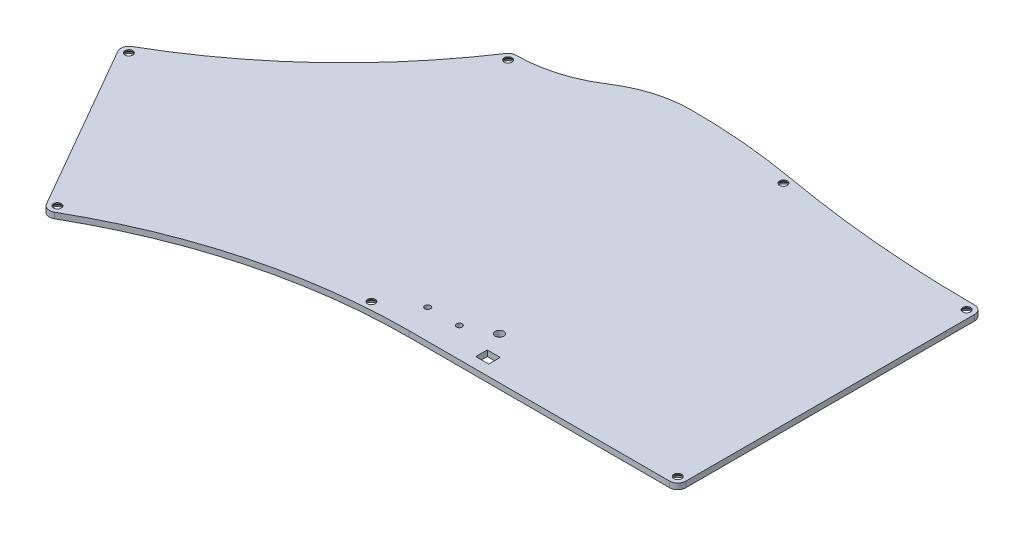
SolidWorks part; units mm, degrees
ref_plane "Front Plane" through (0, 0, 0) normal (0, 0, 1) x (1, 0, 0)
ref_plane "Top Plane" through (0, 0, 0) normal (0, 1, 0) x (1, 0, 0)
ref_plane "Right Plane" through (0, 0, 0) normal (1, 0, 0) x (0, 0, -1)
sketch "Main_line" plane through (0, 0, 0) normal (0, 1, 0) x (1, 0, 0)
  line L17 (146.7823, -115.9715) -> (146.7823, -15.4715)
  line L18 (53.0696, -118.9715) -> (143.7823, -118.9715)
  line L19 (-81.9059, -85.3079) -> (-48.2619, -143.8257)
  line L20 (146.7823, -115.9715) -> (146.7823, -15.4715) construction
  line L21 (53.0696, -118.9715) -> (143.7823, -118.9715) construction
  line L22 (-81.9059, -85.3079) -> (-48.2619, -143.8257) construction
  circle A0 centre (69.7823, -103.9715) radius 1.5 construction
  arc A124 (143.7823, -118.9715) -> (146.7823, -115.9715) centre (143.7823, -115.9715) ccw
  arc A125 (53.0696, -118.9715) -> (-44.1658, -144.9312) centre (53.0696, -314.055) ccw
  arc A126 (-48.2619, -143.8257) -> (-44.1658, -144.9312) centre (-45.6611, -142.3304) ccw
  arc A127 (-80.8004, -81.2119) -> (-81.9059, -85.3079) centre (-79.3051, -83.8126) ccw
  arc A128 (-80.8004, -81.2119) -> (-13.717, -18.312) centre (-180.7133, 92.5689) ccw
  arc A129 (-11.2177, -16.9715) -> (-13.717, -18.312) centre (-11.2177, -19.9715) ccw
  arc A130 (-11.2177, -16.9715) -> (13.3766, -9.6455) centre (-11.2177, 27.9749) ccw
  arc A131 (35.7823, -2.9715) -> (13.3766, -9.6455) centre (35.7823, -43.9179) ccw
  arc A132 (73.4331, -6.2834) -> (35.7823, -2.9715) centre (35.7823, -218.6428) ccw
  arc A133 (73.4331, -6.2834) -> (143.7823, -12.4715) centre (143.7823, 390.502) ccw
  arc A134 (146.7823, -15.4715) -> (143.7823, -12.4715) centre (143.7823, -15.4715) ccw
  arc A135 (143.7823, -118.9715) -> (146.7823, -115.9715) centre (143.7823, -115.9715) ccw construction
  arc A136 (53.0696, -118.9715) -> (-44.1658, -144.9312) centre (53.0696, -314.055) ccw construction
  arc A137 (-48.2619, -143.8257) -> (-44.1658, -144.9312) centre (-45.6611, -142.3304) ccw construction
  arc A138 (-80.8004, -81.2119) -> (-81.9059, -85.3079) centre (-79.3051, -83.8126) ccw construction
  arc A139 (-80.8004, -81.2119) -> (-13.717, -18.312) centre (-180.7133, 92.5689) ccw construction
  arc A140 (-11.2177, -16.9715) -> (-13.717, -18.312) centre (-11.2177, -19.9715) ccw construction
  arc A141 (-11.2177, -16.9715) -> (13.3766, -9.6455) centre (-11.2177, 27.9749) ccw construction
  arc A142 (35.7823, -2.9715) -> (13.3766, -9.6455) centre (35.7823, -43.9179) ccw construction
  arc A143 (73.4331, -6.2834) -> (35.7823, -2.9715) centre (35.7823, -218.6428) ccw construction
  arc A144 (73.4331, -6.2834) -> (143.7823, -12.4715) centre (143.7823, 390.502) ccw construction
  arc A145 (146.7823, -15.4715) -> (143.7823, -12.4715) centre (143.7823, -15.4715) ccw construction
  circle A146 centre (143.7823, -115.9715) radius 1.35 construction
  circle A147 centre (143.7823, -115.9715) radius 1.35 construction
  circle A148 centre (37.7823, -116.5623) radius 1.35 construction
  circle A149 centre (-45.6611, -142.3304) radius 1.35 construction
  circle A150 centre (-79.3051, -83.8126) radius 1.35 construction
  circle A151 centre (-11.2177, -19.9715) radius 1.35 construction
  circle A152 centre (73.7823, -9.2049) radius 1.35 construction
  circle A153 centre (143.7823, -15.4715) radius 1.35 construction
  point P13 (0, 0)
  point P14 (37.7823, -116.5623)
  dimension "D2" = 77
  dimension "D3" = 15
  dimension "D4" = 3
  dimension "D1" = 0
sketch "Sketch1" plane through (0, 0, 0) normal (0, 1, 0) x (1, 0, 0)
  line L17 (-81.7325, -85.2082) -> (-48.0885, -143.726)
  line L18 (53.0696, -118.7715) -> (143.7823, -118.7715)
  line L19 (146.5823, -115.9715) -> (146.5823, -15.4715)
  line L20 (-81.7325, -85.2082) -> (-48.0885, -143.726)
  line L21 (53.0696, -118.7715) -> (143.7823, -118.7715)
  line L22 (146.5823, -115.9715) -> (146.5823, -15.4715)
  circle A93 centre (143.7823, -15.4715) radius 1.35
  circle A94 centre (143.7823, -15.4715) radius 1.35 construction
  circle A95 centre (73.7823, -9.2049) radius 1.35
  circle A96 centre (-11.2177, -19.9715) radius 1.35
  circle A97 centre (-79.3051, -83.8126) radius 1.35
  circle A98 centre (-45.6611, -142.3304) radius 1.35
  circle A99 centre (37.7823, -116.5623) radius 1.35
  circle A100 centre (143.7823, -115.9715) radius 1.35
  circle A101 centre (69.7823, -103.9715) radius 1.5
  circle A102 centre (69.7823, -103.9715) radius 1.5 construction
  arc A103 (-80.7007, -81.3852) -> (-81.7325, -85.2082) centre (-79.3051, -83.8126) ccw
  arc A104 (-48.0885, -143.726) -> (-44.2655, -144.7578) centre (-45.6611, -142.3304) ccw
  arc A105 (53.0696, -118.7715) -> (-44.2655, -144.7578) centre (53.0696, -314.055) ccw
  arc A106 (143.7823, -118.7715) -> (146.5823, -115.9715) centre (143.7823, -115.9715) ccw
  arc A107 (146.5823, -15.4715) -> (143.7823, -12.6715) centre (143.7823, -15.4715) ccw
  arc A108 (73.3982, -6.4803) -> (143.7823, -12.6715) centre (143.7823, 390.502) ccw
  arc A109 (73.3982, -6.4803) -> (35.7823, -3.1715) centre (35.7823, -218.6428) ccw
  arc A110 (35.7823, -3.1715) -> (13.4861, -9.8129) centre (35.7823, -43.9179) ccw
  arc A111 (-11.2177, -17.1715) -> (13.4861, -9.8129) centre (-11.2177, 27.9749) ccw
  arc A112 (-11.2177, -17.1715) -> (-13.5504, -18.4227) centre (-11.2177, -19.9715) ccw
  arc A113 (-80.7007, -81.3852) -> (-13.5504, -18.4227) centre (-180.7133, 92.5689) ccw
  arc A114 (-80.7007, -81.3852) -> (-81.7325, -85.2082) centre (-79.3051, -83.8126) ccw
  arc A115 (-48.0885, -143.726) -> (-44.2655, -144.7578) centre (-45.6611, -142.3304) ccw
  arc A116 (53.0696, -118.7715) -> (-44.2655, -144.7578) centre (53.0696, -314.055) ccw
  arc A117 (143.7823, -118.7715) -> (146.5823, -115.9715) centre (143.7823, -115.9715) ccw
  arc A118 (146.5823, -15.4715) -> (143.7823, -12.6715) centre (143.7823, -15.4715) ccw
  arc A119 (73.3982, -6.4803) -> (143.7823, -12.6715) centre (143.7823, 390.502) ccw
  arc A120 (73.3982, -6.4803) -> (35.7823, -3.1715) centre (35.7823, -218.6428) ccw
  arc A121 (35.7823, -3.1715) -> (13.4861, -9.8129) centre (35.7823, -43.9179) ccw
  arc A122 (-11.2177, -17.1715) -> (13.4861, -9.8129) centre (-11.2177, 27.9749) ccw
  arc A123 (-11.2177, -17.1715) -> (-13.5504, -18.4227) centre (-11.2177, -19.9715) ccw
  arc A124 (-80.7007, -81.3852) -> (-13.5504, -18.4227) centre (-180.7133, 92.5689) ccw
  dimension "D1" = 0.2
extrude "Boss-Extrude1" add sketch "Sketch1" along normal blind 2
sketch "Sketch2" plane through (0, 0, 0) normal (0, -1, 0) x (1, 0, 0)
  circle A0 centre (143.7823, 115.9715) radius 2.5
  circle A1 centre (37.7823, 116.5623) radius 2.5
  circle A2 centre (-45.6611, 142.3304) radius 2.5
  circle A3 centre (-79.3051, 83.8126) radius 2.5
  circle A4 centre (-11.2177, 19.9715) radius 2.5
  circle A5 centre (73.7823, 9.2049) radius 2.5
  circle A6 centre (143.7823, 15.4715) radius 2.5
  dimension "D1" = 5
extrude "Cut-Extrude1" cut sketch "Sketch2" against normal blind 1.7
chamfer "Chamfer1" distance 1.2 angle 45 7 edges at (143.7823, 1.7, 12.9715) (73.7823, 1.7, 6.7049) (-11.2177, 1.7, 17.4715) (-79.3051, 1.7, 81.3126) (-45.6611, 1.7, 139.8304) (37.7823, 1.7, 114.0623) (143.7823, 1.7, 113.4715)
sketch "Sketch3" plane through (0, 0, 0) normal (0, -1, 0) x (1, 0, 0)
  line L0 (53.0696, 118.7715) -> (143.7823, 118.7715) construction
  line L1 (146.5823, 115.9715) -> (146.5823, 15.4715) construction
  circle A0 centre (60.2823, 108.4515) radius 1
  circle A1 centre (49.2823, 108.4515) radius 1
  dimension "D3" = 2
  dimension "D1" = 10.32
  dimension "D2" = 11
  dimension "D4" = 86.3
extrude "Led_hole" cut sketch "Sketch3" against normal through all
sketch "Sketch4" plane through (0, 0, 0) normal (0, -1, 0) x (1, 0, 0)
  line L1 (72.5323, 114.9715) -> (77.0323, 114.9715)
  line L2 (72.5323, 114.9715) -> (72.5323, 110.9715)
  line L3 (72.5323, 110.9715) -> (77.0323, 110.9715)
  line L4 (77.0323, 114.9715) -> (77.0323, 110.9715)
  line L8 (53.0696, 118.7715) -> (143.7823, 118.7715) construction
  line L9 (146.5823, 115.9715) -> (146.5823, 15.4715) construction
  line L10 (72.5323, 114.9715) -> (77.0323, 110.9715) construction
  point P8 (74.7823, 112.9715)
  point P9 (0, 0)
  dimension "D1" = 4
  dimension "D2" = 4.5
  dimension "D5" = 71.8
  dimension "D6" = 5.8
extrude "Cut-Extrude2" cut sketch "Sketch4" against normal through all
